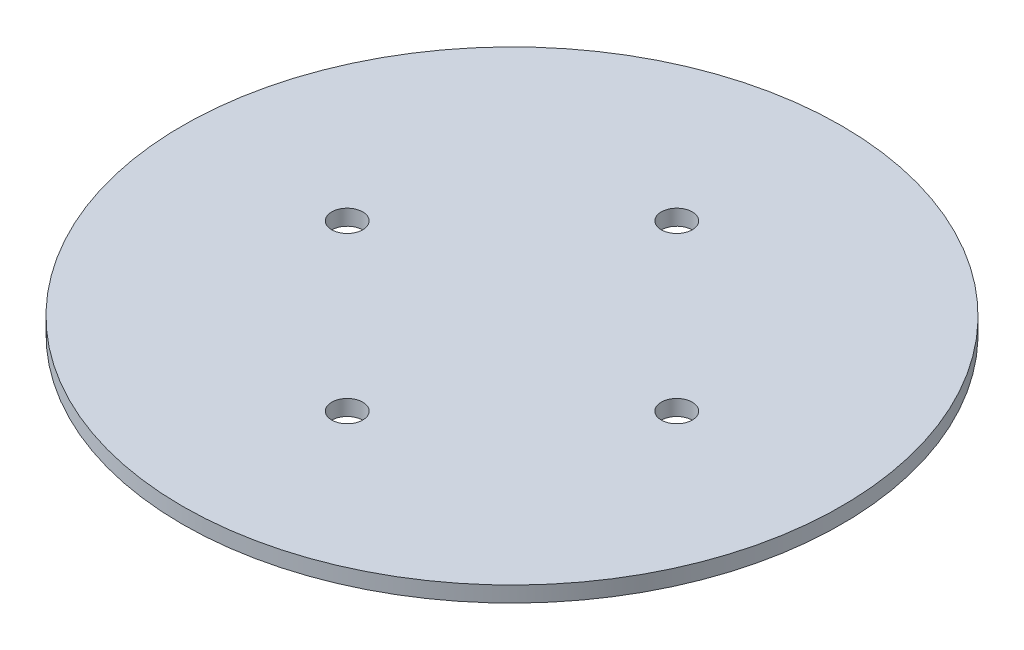
SolidWorks part; units mm, degrees
ref_plane "Front Plane" through (0, 0, 0) normal (0, 0, 1) x (1, 0, 0)
ref_plane "Top Plane" through (0, 0, 0) normal (0, 1, 0) x (1, 0, 0)
ref_plane "Right Plane" through (0, 0, 0) normal (1, 0, 0) x (0, 0, -1)
sketch "Sketch2" plane through (0, 0, 0) normal (0, 1, 0) x (1, 0, 0)
  circle A0 centre (0, 0) radius 25.5
base flange "Base-Flange1" sketch "Sketch2" thickness 1.21 reverse thickness direction no parameters "D1"=0.762
sketch "Sketch7" plane through (0, 0, 0) normal (0, 1, 0) x (1, 0, 0)
  line L0 (0, -25.5) -> (0, 25.5)
  line L1 (-25.5, 0) -> (25.5, 0)
  circle A0 centre (0, 0) radius 25.5 construction
  point P7 (0, 0)
  dimension "D1" = 90
  dimension "D2" = 0
hole_wizard "M2 Clearance Hole1" positions "Sketch11" profile "Sketch10" hole size "M2" standard "ANSI Metric"
sketch "Sketch11" plane through (0, -1.21, 0) normal (0, -1, 0) x (-1, 0, 0)
  point P0 (0, -12.75)
  point P2 (-12.75, 0)
  point P4 (12.75, 0)
  point P6 (0, 12.75)
  dimension "D1" = 12.75
  dimension "D2" = 12.75
  dimension "D3" = 12.75
  dimension "D4" = 12.75
sketch "Sketch10" plane through (0, -1.21, 12.75) normal (1, 0, 0) x (0, 0, -1)
  line L0 (0, 0) -> (0, 10.721)
  line L1 (0, 10.721) -> (1.2, 10)
  line L2 (1.2, 10) -> (1.2, 0)
  line L5 (1.2, 0) -> (0, 0)
  line L10 (0, 10.721) -> (-1.2, 10) construction
  line L11 (0, -6.35) -> (0, 107.95) construction
  dimension "Hole Dia." = 2.4
  dimension "Hole Depth" = 10
  dimension "Drill Angle" = 118
sketch "Bend-Lines1" [suppressed] plane through (0, 0, 0) normal (0, 1, 0) x (1, 0, 0)
sketch "Bounding-Box1" [suppressed] plane through (0, 0, 0) normal (0, 1, 0) x (1, 0, 0)
sheet metal parameters "Sheet-Metal(1)" thickness 1.21 parameters "D1"=0.762
flat pattern "Flat-Pattern(1)" [suppressed]
sketch "Bend-Lines2" plane through (0, 0, 0) normal (0, 1, 0) x (1, 0, 0)
sketch "Bounding-Box2" [suppressed] plane through (0, 0, 0) normal (0, 1, 0) x (1, 0, 0)
sheet metal parameters "Sheet-Metal(2)" thickness 1.21 parameters "D1"=0.762
flat pattern "Flat-Pattern(1)"
sketch "Bend-Lines2" plane through (0, 0, 0) normal (0, 1, 0) x (1, 0, 0)
sketch3d "Bounding-Box2" [suppressed]
  line L0 (25.55, -25.4499, 0) -> (-25.4499, -25.5499, 0) construction
  line L1 (25.45, 25.5499, 0) -> (-25.5499, 25.4499, 0) construction
  line L2 (25.55, -25.4499, 0) -> (25.45, 25.5499, 0) construction
  line L3 (-25.4499, -25.5499, 0) -> (-25.5499, 25.4499, 0) construction
